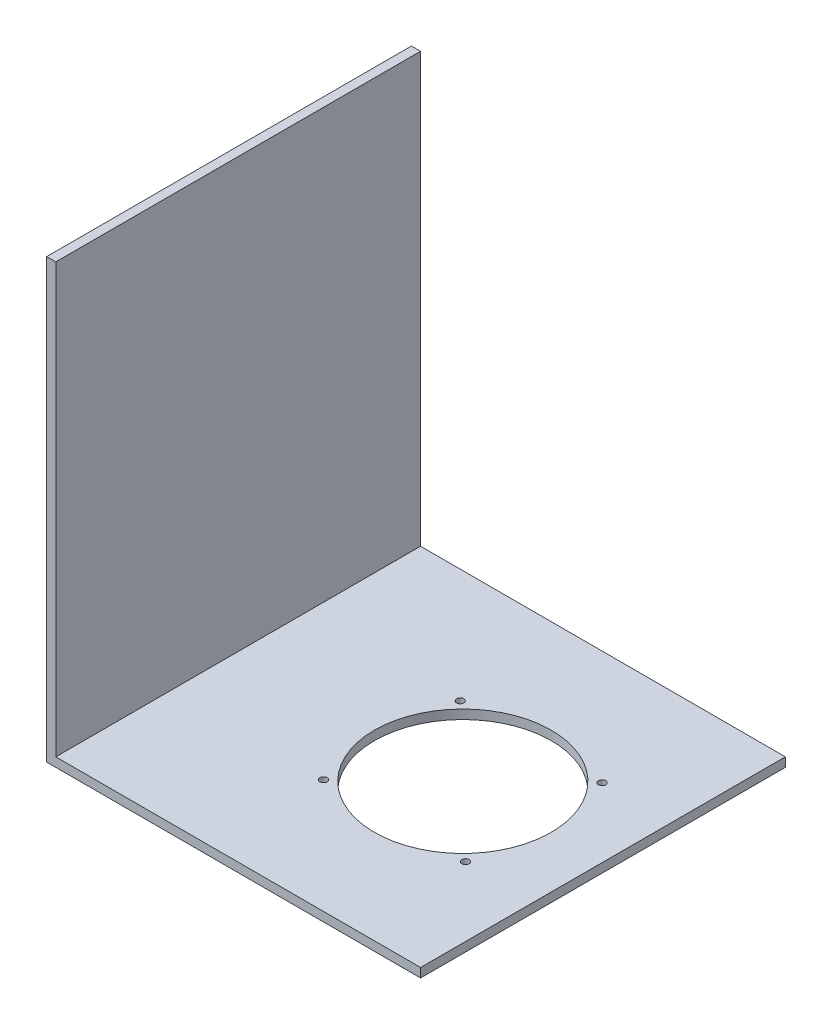
SolidWorks part; units mm, degrees
ref_plane "Front Plane" through (0, 0, 0) normal (0, 0, 1) x (1, 0, 0)
ref_plane "Top Plane" through (0, 0, 0) normal (0, 1, 0) x (1, 0, 0)
ref_plane "Right Plane" through (0, 0, 0) normal (1, 0, 0) x (0, 0, -1)
sketch "Sketch1" plane through (0, 0, 0) normal (0, 0, 1) x (1, 0, 0)
  line L0 (0, 240) -> (0, 0)
  line L1 (0, 0) -> (205, 0)
  line L2 (205, 0) -> (205, 5)
  line L3 (205, 5) -> (5, 5)
  line L4 (5, 5) -> (5, 240)
  line L5 (5, 240) -> (0, 240)
  dimension "D1" = 5
  dimension "D2" = 5
  dimension "D3" = 200
  dimension "D4" = 235
extrude "Boss-Extrude1" add sketch "Sketch1" along normal blind 200
sketch "Sketch2" plane through (0, 5, 0) normal (0, 1, 0) x (1, 0, 0)
  line L0 (205, -100) -> (0, -100) construction
  line L1 (205, -200) -> (205, 0) construction
  line L2 (0, -200) -> (0, 0) construction
  line L4 (167.0574, -137.4644) -> (89.2778, -137.4644) construction
  line L5 (167.0574, -137.4644) -> (167.0574, -62.5356) construction
  line L6 (167.0574, -62.5356) -> (89.2778, -62.5356) construction
  line L7 (89.2778, -137.4644) -> (89.2778, -62.5356) construction
  line L8 (167.0574, -137.4644) -> (89.2778, -62.5356) construction
  line L9 (167.0574, -62.5356) -> (89.2778, -137.4644) construction
  circle A0 centre (128.1676, -100) radius 48.5
  circle A1 centre (89.2778, -62.5356) radius 2
  circle A2 centre (167.0574, -62.5356) radius 2
  circle A3 centre (89.2778, -137.4644) radius 2
  circle A4 centre (167.0574, -137.4644) radius 2
  dimension "D1" = 97
  dimension "D2" = 4
  dimension "D3" = 108
extrude "Cut-Extrude1" cut sketch "Sketch2" against normal up to next
